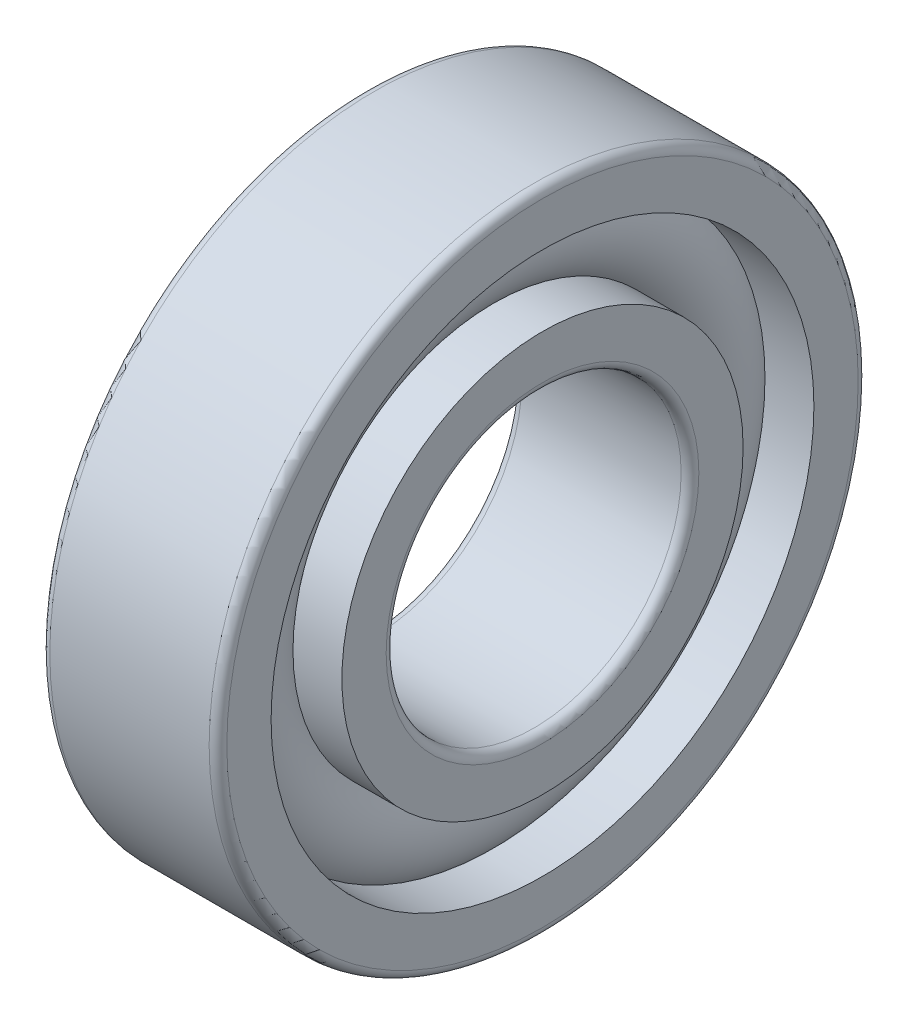
SolidWorks part; units mm, degrees
ref_plane "Plane1" through (0, 0, 0) normal (0, 0, 1) x (1, 0, 0)
ref_plane "Plane2" through (0, 0, 0) normal (0, 1, 0) x (1, 0, 0)
ref_plane "Plane3" through (0, 0, 0) normal (1, 0, 0) x (0, 0, -1)
sketch "Clipboard" plane through (0, 0, 0) normal (0, 0, 1) x (1, 0, 0)
  line L0 (-10, 0) -> (10, 0) construction
  line L1 (0, 0) -> (22.3471, -0.7804)
  line L2 (0, 0) -> (7.9951, 0.2792)
  line L3 (0, 0) -> (22.3471, -0.7804)
  line L4 (0, 0) -> (-22.3573, -0.3902)
  dimension "BallCLRad" = 8
sketch "CagSpiSke" plane through (0, 0, 0) normal (0, 0, 1) x (1, 0, 0)
  line L0 (0.18, 7.7) -> (0.18, 8.3)
  line L1 (0.18, 8.3) -> (-0.18, 8.3)
  line L2 (-0.18, 8.3) -> (-0.18, 7.7)
  line L3 (-0.18, 7.7) -> (0.18, 7.7)
  line L4 (-20.6375, 0) -> (20.6375, 0) construction
  line L5 (0, 0) -> (0, 23.7692) construction
  dimension "OD" = 16.6
  dimension "ID" = 15.4
revolve "CageSpine" add sketch "CagSpiSke" angle 0.001 about L4 reverse direction yes
ref_axis "Axis1" through (-50, 0, 0) along (1, 0, 0)
sketch "CagBalSke" plane through (0, 0, 0) normal (0, 0, 1) x (1, 0, 0)
  line L0 (-1.98, 8) -> (1.98, 8)
  line L1 (-1.905, 8) -> (1.905, 8) construction
  line L2 (-10, 0) -> (10, 0) construction
  line L3 (0, 0) -> (0, 24) construction
  arc A0 (1.98, 8) -> (-1.98, 8) centre (0, 8) cw
  dimension "BallCLRad" = 8
revolve "CageBall" [suppressed] add sketch "CagBalSke" angle 360 about L1 reverse direction yes
pattern_circular "CageBalls" [suppressed] count 2 every 180 about axis through (-50, 0, 0) along (1, 0, 0)
sketch "CagTrmODSke" plane through (0, 0, 0) normal (0, 0, 1) x (1, 0, 0)
  line L0 (1.981, 8.3) -> (1.981, 9.981)
  line L1 (1.981, 9.981) -> (-1.981, 9.981)
  line L2 (-1.981, 9.981) -> (-1.981, 8.3)
  line L3 (-1.981, 8.3) -> (1.981, 8.3)
  line L4 (-20.6375, 0) -> (20.6375, 0) construction
  line L5 (0, 0) -> (0, 25) construction
  dimension "Width" = 3.962
  dimension "ID" = 16.6
  dimension "OD" = 19.962
revolve "CageTrimOD" [suppressed] cut sketch "CagTrmODSke" angle 360 about L4 reverse direction yes
sketch "CagTrmIDSke" plane through (0, 0, 0) normal (0, 0, 1) x (1, 0, 0)
  line L0 (1.981, 6.021) -> (1.981, 7.7)
  line L1 (1.981, 7.7) -> (-1.981, 7.7)
  line L2 (-1.981, 7.7) -> (-1.981, 6.021)
  line L3 (-1.981, 6.021) -> (1.981, 6.021)
  line L4 (-20.6375, 0) -> (20.6375, 0) construction
  line L5 (0, 0) -> (0, 25) construction
  dimension "Width" = 3.962
  dimension "ID" = 12.042
  dimension "OD" = 15.4
revolve "CageTrimID" [suppressed] cut sketch "CagTrmIDSke" angle 360 about L4 reverse direction yes
sketch "BalSimSke" plane through (0, 0, 0) normal (0, 0, 1) x (1, 0, 0)
  line L0 (-10, 0) -> (10, 0) construction
  line L1 (-10, 8) -> (10, 8) construction
  line L2 (0, 0) -> (0, 23) construction
  circle A0 centre (0, 8) radius 1.8
  dimension "BallCLRad" = 8
  dimension "Ball_diameter" = 3.6
revolve "BallsSimplified" add sketch "BalSimSke" angle 360 about L0
sketch "BalDetSke" plane through (0, 0, 0) normal (0, 0, 1) x (1, 0, 0)
  line L0 (-1.8, 8) -> (1.8, 8)
  line L1 (-1.905, 8) -> (1.905, 8) construction
  line L2 (0, 0) -> (0, 25) construction
  arc A0 (1.8, 8) -> (-1.8, 8) centre (0, 8) cw
  dimension "BallCLRad" = 8
  dimension "Ball_diameter" = 3.6
revolve "BallDetailed" [suppressed] add sketch "BalDetSke" angle 360 about L1 reverse direction yes
sketch "InnRacSke" plane through (0, 0, 0) normal (0, 0, 1) x (1, 0, 0)
  line L0 (-1.3079, 6.8) -> (-3, 6.8)
  line L1 (-3, 6.8) -> (-3, 5.3)
  line L2 (-2.7, 5) -> (2.7, 5)
  line L3 (3, 5.3) -> (3, 6.8)
  line L4 (3, 6.8) -> (1.3079, 6.8)
  line L5 (-20.6375, 0) -> (20.6375, 0) construction
  line L6 (0, 0) -> (0, 30) construction
  arc A0 (-3, 5.3) -> (-2.7, 5) centre (-2.7, 5.3) ccw
  arc A1 (2.7, 5) -> (3, 5.3) centre (2.7, 5.3) ccw
  arc A2 (1.3079, 6.8) -> (-1.3079, 6.8) centre (0, 8) cw
  dimension "BallCLRad" = 8
  dimension "Fillet_radius" = 0.3
  dimension "Ball_diameter" = 3.55
  dimension "ID" = 10
  dimension "OD" = 13.6
  dimension "Width" = 6
revolve "InnerRace" add sketch "InnRacSke" angle 360 about L5 reverse direction yes
sketch "OutRacSke" plane through (0, 0, 0) normal (0, 0, 1) x (1, 0, 0)
  line L0 (-1.3079, 9.2) -> (-3, 9.2)
  line L1 (-3, 9.2) -> (-3, 10.7)
  line L2 (-2.7, 11) -> (2.7, 11)
  line L3 (3, 10.7) -> (3, 9.2)
  line L4 (3, 9.2) -> (1.3079, 9.2)
  line L5 (-20.6375, 0) -> (20.6375, 0) construction
  line L6 (0, 0) -> (0, 30) construction
  arc A0 (-3, 10.7) -> (-2.7, 11) centre (-2.7, 10.7) cw
  arc A1 (2.7, 11) -> (3, 10.7) centre (2.7, 10.7) cw
  arc A2 (1.3079, 9.2) -> (-1.3079, 9.2) centre (0, 8) ccw
  dimension "BallCLRad" = 8
  dimension "Fillet_radius" = 0.3
  dimension "Ball_diameter" = 3.55
  dimension "Width" = 6
revolve "OuterRace" add sketch "OutRacSke" angle 360 about L5 reverse direction yes
pattern_circular "BallsDetailed" [suppressed] count 2 every 180 about axis through (-50, 0, 0) along (1, 0, 0)
equation "\"BallCLRad@Clipboard\" = ( \"OD@OutRacSke\" + \"ID@InnRacSke\" ) / 4"
equation "\"BallCLRad@BalSimSke\" = \"BallCLRad@Clipboard\""
equation "\"BallCLRad@BalDetSke\" = \"BallCLRad@Clipboard\""
equation "\"BallCLRad@InnRacSke\" = \"BallCLRad@Clipboard\""
equation "\"BallCLRad@OutRacSke\" = \"BallCLRad@Clipboard\""
equation "\"Ball_diameter@InnRacSke\" = \"Ball_diameter@BalDetSke\" - 0.05"
equation "\"Ball_diameter@OutRacSke\" = \"Ball_diameter@BalDetSke\" - 0.05"
equation "\"Ball_diameter@BalSimSke\" = \"Ball_diameter@BalDetSke\""
equation "\"Width@OutRacSke\" = \"Width@InnRacSke\""
equation "\"Fillet_radius@OutRacSke\" = \"Fillet_radius@InnRacSke\""
equation "\"Max_count@Clipboard\" = int( 3.14159265 / atn(( \"Ball_diameter@BalDetSke\" / 2) / sqr( \"BallCLRad@Clipboard\"  *  \"BallCLRad@Clipboard\" - ( \"Ball_diameter@BalDetSke\" / 2) *  ( \"Ball_diameter@BalDetSke\" / 2))))"
equation "\"Max_count@Clipboard\" = ((sgn( \"Max_count@Clipboard\" - \"Count@Clipboard\" )-1)*( \"Max_count@Clipboard\" - \"Count@Clipboard\" ))/-2+ \"Count@Clipboard\""
equation "\"Count@BallsDetailed\" = int( \"Show_count@Clipboard\" ) "
equation "\"Count@BallsDetailed\" = ((sgn( \"Count@BallsDetailed\" - \"Max_count@Clipboard\" )-1)*( \"Count@BallsDetailed\" - \"Max_count@Clipboard\" ))/-2+ \"Max_count@Clipboard\""
equation "\"Count@BallsDetailed\" = ((sgn( \"Count@BallsDetailed\" - \"Min_count@Clipboard\" )+1)*( \"Count@BallsDetailed\" - \"Min_count@Clipboard\"))/2 +\"Min_count@Clipboard\""
equation "\"Angle@BallsDetailed\" = 360.0 / \"Max_count@Clipboard\""
equation "\"BallCLRad@CagBalSke\" = \"BallCLRad@Clipboard\""
equation "\"Count@CageBalls\" = \"Count@BallsDetailed\""
equation "\"Angle@CageBalls\" = \"Angle@BallsDetailed\""
equation "\"Angle@CageSpine\" =  \"Angle@CageBalls\" * ( \"Count@CageBalls\" -1 + int( \"Count@CageBalls\" / \"Max_count@Clipboard\" ) )  + 0.001 -  int( \"Count@CageBalls\" / \"Max_count@Clipboard\" ) * 0.001"
equation "\"Angle@CageSpine\" =  \"Angle@CageSpine\" * int( \"Min_count@Clipboard\" / 2) + int(1 / \"Min_count@Clipboard\")  * 0.001"
equation "\"CageWallOD@CagBalSke\" =  \"Ball_diameter@BalDetSke\" * 1.1"
equation "\"Thickness@CagSpiSke\" =  \"Ball_diameter@BalDetSke\" * 0.1"
equation "\"OD@CagTrmODSke\" = \"BallCLRad@Clipboard\" * 2 + \"CageWallOD@CagBalSke\" + 0.002"
equation "\"ID@CagTrmODSke\" = \"BallCLRad@Clipboard\" * 2 + \"Ball_diameter@BalDetSke\" / 6"
equation "\"OD@CagTrmIDSke\" = \"BallCLRad@Clipboard\" * 2 - \"Ball_diameter@BalDetSke\" / 6"
equation "\"ID@CagTrmIDSke\" = \"BallCLRad@Clipboard\" * 2 - \"CageWallOD@CagBalSke\" + 0.002"
equation "\"OD@CagSpiSke\" = \"ID@CagTrmODSke\""
equation "\"ID@CagSpiSke\" = \"OD@CagTrmIDSke\""
equation "\"Width@CagTrmODSke\" = \"CageWallOD@CagBalSke\" + 0.002"
equation "\"Width@CagTrmIDSke\" = \"CageWallOD@CagBalSke\" + 0.002"
